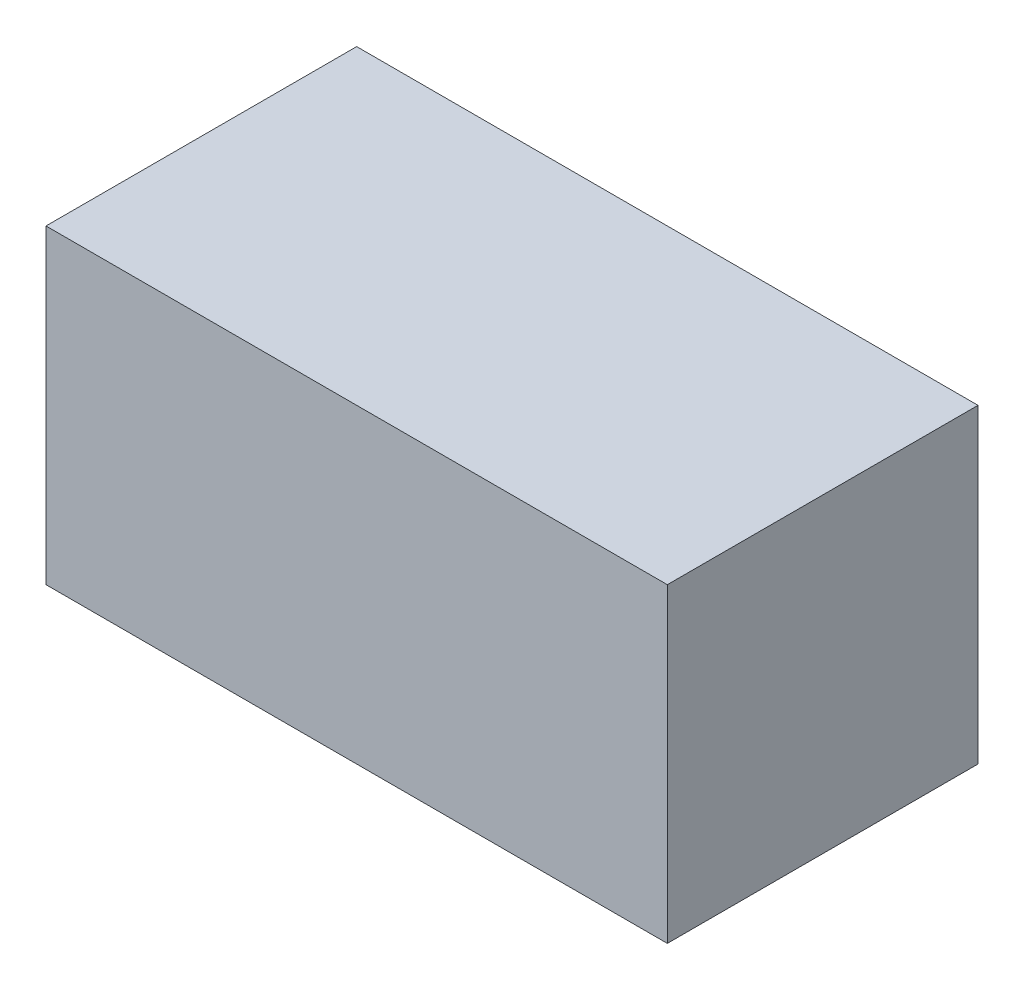
SolidWorks part; units mm, degrees
ref_plane "前视基准面" through (0, 0, 0) normal (0, 0, 1) x (1, 0, 0)
ref_plane "上视基准面" through (0, 0, 0) normal (0, 1, 0) x (1, 0, 0)
ref_plane "右视基准面" through (0, 0, 0) normal (1, 0, 0) x (0, 0, -1)
other "Configuration Table"
sketch "草图1" plane through (0, 0, 0) normal (0, 0, 1) x (1, 0, 0)
  line L0 (0, -3.2665) -> (0, 3.8924) construction
  line L2 (0, 0) -> (100, 0)
  line L3 (0, 0) -> (0, -50)
  line L4 (0, -50) -> (100, -50)
  line L5 (100, 0) -> (100, -50)
  dimension "D1" = 100
  dimension "D2" = 50
extrude "凸台-拉伸1" add sketch "草图1" against normal blind 50 contours L3 L2 L5 L4
sketch "草图2" plane through (0, 0, 0) normal (0, 1, 0) x (1, 0, 0)
  line L0 (100, 50) -> (150, 78.8675)
  line L1 (150, 78.8675) -> (182.8934, 21.8945)
  line L2 (0, 50) -> (100, 50) construction
  line L3 (100, 50) -> (100, 0) construction
  line L4 (100, 0) -> (171.6506, 41.3675)
  dimension "D1" = 30
  dimension "D2" = 50
